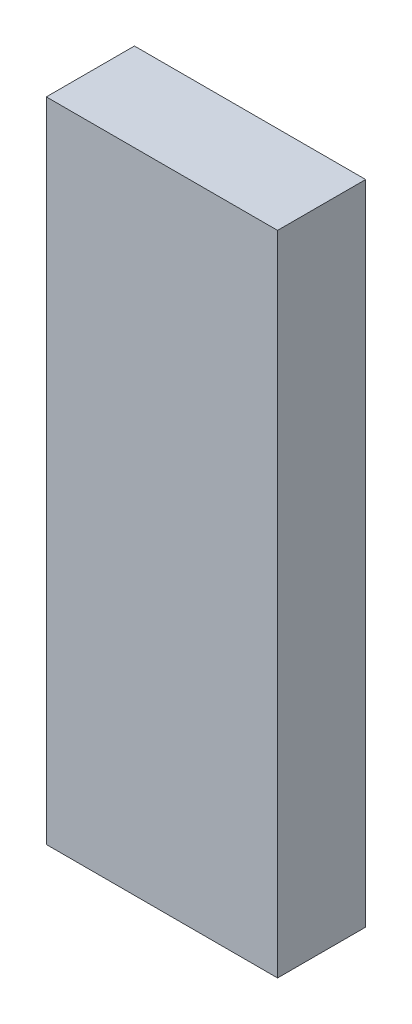
SolidWorks part; units mm, degrees
material "POLYURETHANE (11671)"
ref_plane "Front Plane" through (0, 0, 0) normal (0, 0, 1) x (1, 0, 0)
ref_plane "Top Plane" through (0, 0, 0) normal (0, 1, 0) x (1, 0, 0)
ref_plane "Right Plane" through (0, 0, 0) normal (1, 0, 0) x (0, 0, -1)
sketch "Sketch1" plane through (0, 0, 0) normal (0, 0, 1) x (1, 0, 0)
  line L1 (-12.5, 35) -> (12.5, 35)
  line L2 (-12.5, 35) -> (-12.5, -35)
  line L3 (-12.5, -35) -> (12.5, -35)
  line L4 (12.5, 35) -> (12.5, -35)
  line L5 (-12.5, 35) -> (12.5, -35) construction
  line L6 (-12.5, -35) -> (12.5, 35) construction
  point P0 (0, 0)
  dimension "D1" = 25
  dimension "D2" = 70
extrude "Boss-Extrude1" add sketch "Sketch1" along normal blind 9.525
